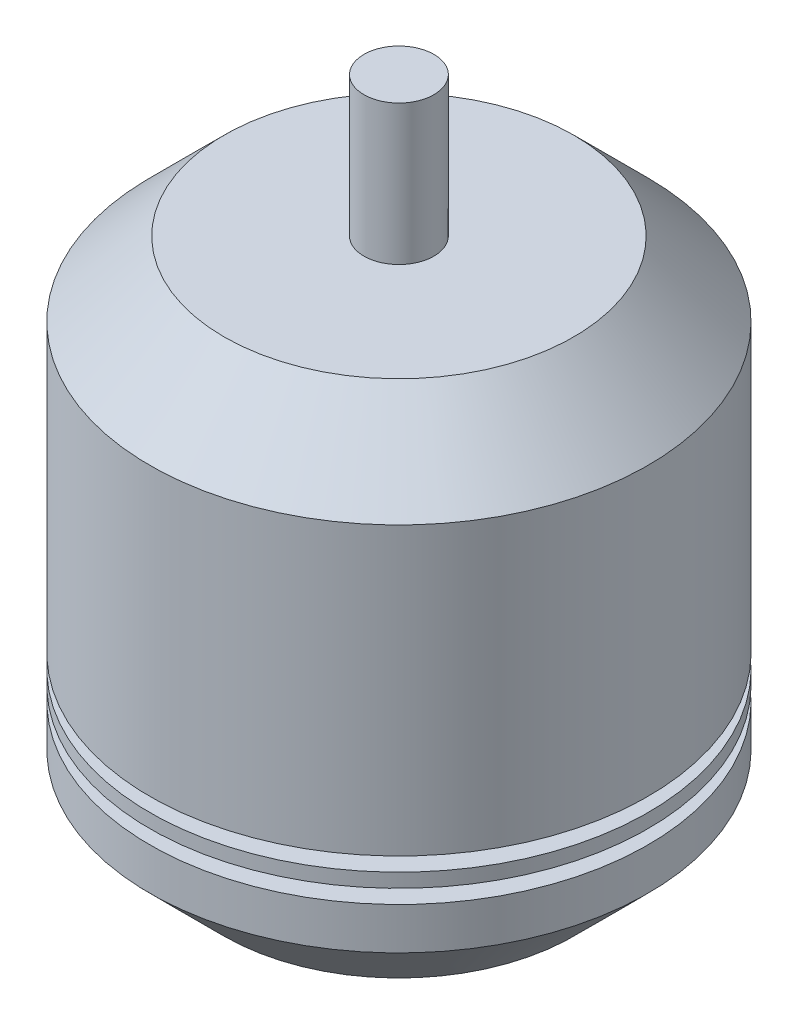
SolidWorks part; units mm, degrees
ref_plane "Front Plane" through (0, 0, 0) normal (0, 0, 1) x (1, 0, 0)
ref_plane "Top Plane" through (0, 0, 0) normal (0, 1, 0) x (1, 0, 0)
ref_plane "Right Plane" through (0, 0, 0) normal (1, 0, 0) x (0, 0, -1)
sketch "Sketch1" plane through (0, 0, 0) normal (0, 0, 1) x (1, 0, 0)
  line L0 (6.35, -2.1958) -> (63.5, -2.1958)
  line L1 (63.5, -2.1958) -> (90.4408, 24.745)
  line L2 (90.4408, 24.745) -> (90.4408, 39.985)
  line L3 (90.4408, 159.365) -> (63.5, 186.3058)
  line L4 (63.5, 186.3058) -> (12.7, 186.3058)
  line L5 (12.7, 186.3058) -> (12.7, 237.1058)
  line L6 (12.7, 237.1058) -> (0, 237.1058)
  line L7 (0, 237.1058) -> (0, 0)
  line L8 (0, 0) -> (0, -25.465)
  line L9 (0, -25.465) -> (6.35, -25.465)
  line L10 (6.35, -25.465) -> (6.35, -2.1958)
  line L11 (22.9673, 176.1458) -> (62.5008, 176.1458)
  line L12 (62.5008, 176.1458) -> (80.2808, 158.3658)
  line L13 (80.2808, 158.3658) -> (80.2808, 140.5858)
  line L14 (80.2808, 140.5858) -> (12.8073, 140.5858)
  line L15 (12.8073, 140.5858) -> (12.8073, 165.9858)
  line L16 (12.8073, 165.9858) -> (22.9673, 165.9858)
  line L17 (22.9673, 165.9858) -> (22.9673, 176.1458)
  line L18 (90.4408, 55.225) -> (80.2808, 55.225)
  line L19 (80.2808, 55.225) -> (80.2808, 50.145)
  line L20 (80.2808, 50.145) -> (90.4408, 50.145)
  line L21 (90.4408, 45.065) -> (80.2808, 45.065)
  line L22 (80.2808, 45.065) -> (80.2808, 39.985)
  line L23 (80.2808, 39.985) -> (90.4408, 39.985)
  line L24 (90.4408, 55.225) -> (90.4408, 159.365)
  line L25 (90.4408, 45.065) -> (90.4408, 50.145)
  line L26 (0, 237.1058) -> (0, 290.721) construction
  dimension "D1" = 50.8
  dimension "D2" = 50.8
  dimension "D3" = 12.7
  dimension "D4" = 38.1
  dimension "D5" = 38.1
  dimension "D6" = 134.62
  dimension "D7" = 6.35
  dimension "D8" = 45
  dimension "D9" = 45
  dimension "D10" = 25.465
  dimension "D11" = 237.1058
  dimension "D12" = 10.16
  dimension "D13" = 10.16
  dimension "D14" = 45
  dimension "D15" = 10.16
  dimension "D16" = 10.16
  dimension "D17" = 12.8073
  dimension "D18" = 25.4
  dimension "D19" = 17.78
  dimension "D20" = 10.16
  dimension "D21" = 5.08
  dimension "D22" = 5.08
  dimension "D23" = 5.08
  dimension "D24" = 10.16
  dimension "D25" = 15.24
ref_axis "Axis1" through (0, 237.1058, 0) along (0, 1, 0)
revolve "Revolve1" add sketch "Sketch1" angle 360 about L26
